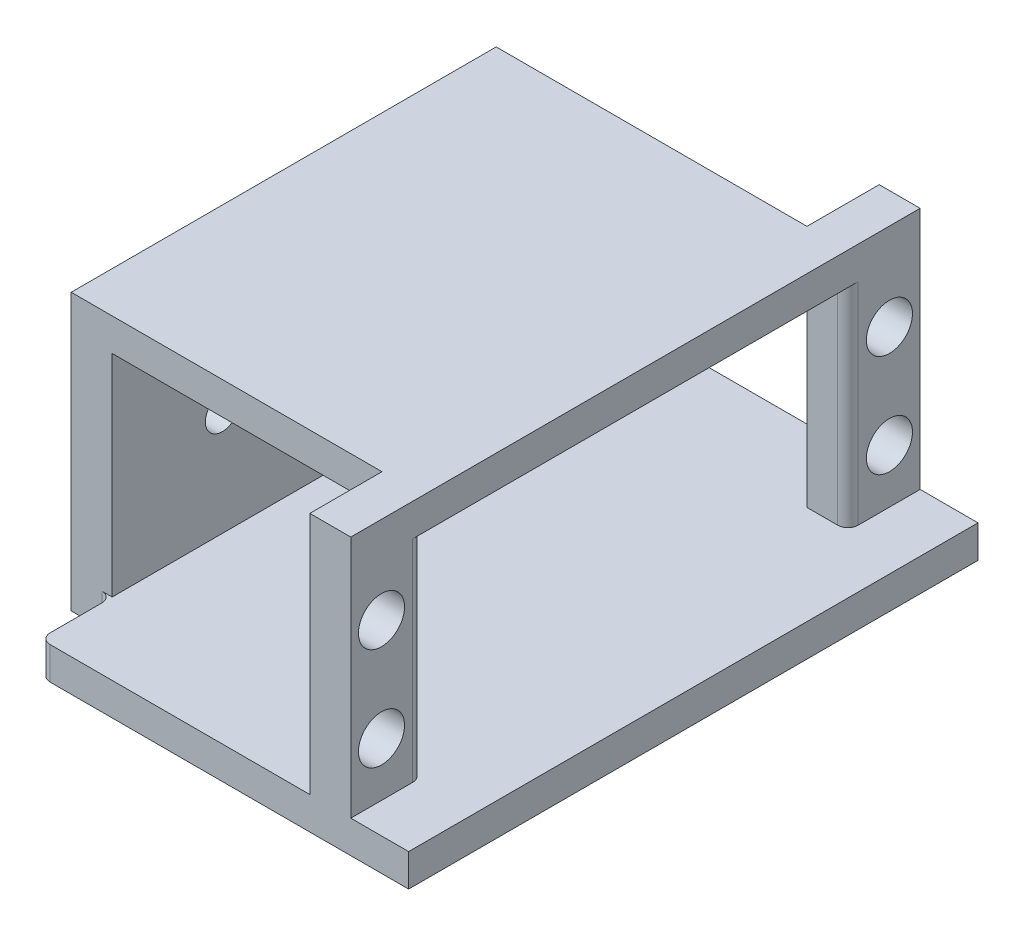
SolidWorks part; units mm, degrees
ref_plane "Front Plane" through (0, 0, 0) normal (0, 0, 1) x (1, 0, 0)
ref_plane "Top Plane" through (0, 0, 0) normal (0, 1, 0) x (1, 0, 0)
ref_plane "Right Plane" through (0, 0, 0) normal (1, 0, 0) x (0, 0, -1)
sketch "Sketch1" plane through (0, 0, 0) normal (0, 1, 0) x (1, 0, 0)
  line L1 (-20, 27.8) -> (20, 27.8)
  line L2 (-20, 27.8) -> (-20, -27.8)
  line L3 (-20, -27.8) -> (20, -27.8)
  line L4 (20, 27.8) -> (20, -27.8)
  line L5 (-20, 27.8) -> (20, -27.8) construction
  line L6 (-20, -27.8) -> (20, 27.8) construction
  point P0 (0, 0)
  dimension "D1" = 55.6
  dimension "D2" = 40
extrude "Boss-Extrude1" add sketch "Sketch1" along normal blind 3.175
sketch "Sketch2" plane through (0, 3.175, 0) normal (0, 1, 0) x (1, 0, 0)
  line L0 (-20, 27.8) -> (-20, -27.8) construction
  line L1 (-16, 20.75) -> (-20, 20.75)
  line L2 (-16, 20.75) -> (-16, -20.75)
  line L3 (-16, -20.75) -> (-20, -20.75)
  line L4 (-20, 20.75) -> (-20, -20.75)
  line L5 (-16, 20.75) -> (-20, -20.75) construction
  line L6 (-16, -20.75) -> (-20, 20.75) construction
  line L8 (-20, -27.8) -> (20, -27.8) construction
  line L9 (-20, 0) -> (65.8452, 0) construction
  line L12 (10.35, 27.8) -> (10.35, 20.75)
  line L13 (14.35, -27.8) -> (10.35, -27.8)
  line L14 (14.35, -27.8) -> (14.35, -20.75)
  line L15 (14.35, -20.75) -> (10.35, -20.75)
  line L16 (10.35, -27.8) -> (10.35, -20.75)
  line L17 (14.35, 20.75) -> (10.35, 20.75)
  line L18 (14.35, 27.8) -> (14.35, 20.75)
  line L19 (14.35, 27.8) -> (10.35, 27.8)
  line L27 (-5.55, 20.1) -> (14.25, 20.1) construction
  line L28 (-5.55, -20.1) -> (14.25, -20.1) construction
  line L30 (20, -27.8) -> (20, 27.8) construction
  point P0 (-18, 0)
  dimension "D1" = 4
  dimension "D4" = 4
  dimension "D6" = 7.05
  dimension "D9" = 41.5
  dimension "D2" = 41.5
  dimension "D3" = 0.65
  dimension "D7" = 0.65
  dimension "D5" = 5.65
extrude "Boss-Extrude2" add sketch "Sketch2" along normal blind 20.6
sketch "Sketch3" plane through (0, 23.775, 0) normal (0, 1, 0) x (1, 0, 0)
  line L0 (-20, 20.75) -> (10.35, 20.75)
  line L16 (14.35, -27.8) -> (10.35, -27.8)
  line L17 (10.35, -27.8) -> (10.35, -20.75)
  line L18 (10.35, -20.75) -> (-20, -20.75)
  line L19 (-20, -20.75) -> (-20, 20.75)
  line L20 (10.35, 20.75) -> (10.35, 27.8)
  line L21 (10.35, 27.8) -> (14.35, 27.8)
  line L22 (14.35, 27.8) -> (14.35, -27.8)
extrude "Boss-Extrude3" add sketch "Sketch3" along normal blind 3.175
sketch "Sketch5" plane through (14.35, 0, 0) normal (1, 0, 0) x (0, 0, -1)
  line L0 (-27.8, 26.95) -> (-27.8, 3.175) construction
  line L1 (-27.8, 3.175) -> (-20.75, 3.175) construction
  line L2 (0, 0) -> (0, 26.95) construction
  line L3 (-27.8, 26.95) -> (27.8, 26.95) construction
  circle A0 centre (-24.8, 8.425) radius 2.25
  circle A1 centre (-24.8, 18.425) radius 2.25
  circle A2 centre (24.8, 18.425) radius 2.25
  circle A3 centre (24.8, 8.425) radius 2.25
  dimension "D1" = 4.5
  dimension "D3" = 5.25
  dimension "D2" = 3
  dimension "D4" = 10
extrude "Cut-Extrude2" cut sketch "Sketch5" against normal up to surface (4 mm away) up to face at (10.35, 16.805, 23.57)
sketch "Sketch6" plane through (-20, 0, 0) normal (-1, 0, 0) x (0, 0, 1)
  circle A0 centre (10, 13.43) radius 1.65
  dimension "D1" = 3.3
extrude "Cut-Extrude3" cut sketch "Sketch6" against normal up to surface (4 mm away) contours A0 up to face at (-16, 13.475, 0)
fillet "Fillet1" radius 1 2 edges at (14.35, 13.475, 20.75) (14.35, 13.475, -20.75)
sketch "Sketch7" plane through (0, 3.175, 0) normal (0, 1, 0) x (1, 0, 0)
  line L1 (-20, -27.8) -> (-16, -27.8)
  line L2 (-20, -27.8) -> (-20, -20.75)
  line L3 (-20, -20.75) -> (-16, -20.75)
  line L4 (-16, -27.8) -> (-16, -20.75)
  line L5 (-20, 27.8) -> (-16, 27.8)
  line L6 (-20, 27.8) -> (-20, 20.75)
  line L7 (-20, 20.75) -> (-16, 20.75)
  line L8 (-16, 27.8) -> (-16, 20.75)
extrude "Cut-Extrude4" cut sketch "Sketch7" against normal up to surface (3.175 mm away) up to face at (0, 0, 0)
fillet "Fillet2" radius 1 4 edges at (-16, 1.5875, 27.8) (-16, 1.5875, 20.75) (-16, 1.5875, -20.75) (-16, 1.5875, -27.8)
sketch "Sketch8" plane through (0, 0, 0) normal (0, -1, 0) x (1, 0, 0)
  line L0 (-20, 0) -> (20, 0) construction
  line L1 (-20, -20.75) -> (-20, 20.75) construction
  line L2 (20, 27.8) -> (20, -27.8) construction
  line L3 (2.5, 27.8) -> (2.5, -27.8) construction
  line L5 (-15, 27.8) -> (20, 27.8) construction
  line L6 (20, -27.8) -> (-15, -27.8) construction
  circle A0 centre (2.5, 0) radius 4
  dimension "D1" = 8
extrude "Boss-Extrude4" add sketch "Sketch8" along normal blind 7
equation "\"D4@Sketch2\"=\"D1@Sketch2\""
equation "\"D2@Sketch2\"=\"D9@Sketch2\""
